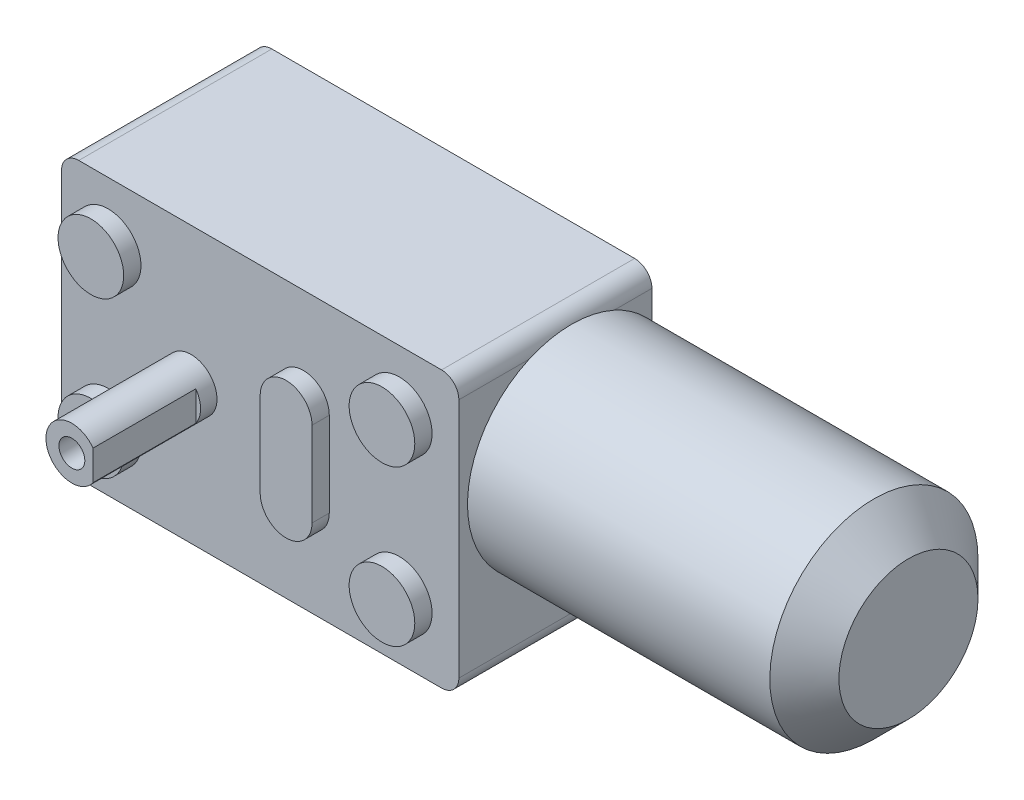
SolidWorks part; units mm, degrees
ref_plane "Front Plane" through (0, 0, 0) normal (1, 0, 0) x (0, 1, 0)
ref_plane "Top Plane" through (0, 0, 0) normal (0, 0, 1) x (0, 1, 0)
ref_plane "Right Plane" through (0, 0, 0) normal (0, 1, 0) x (-1, 0, 0)
sketch "Sketch1" plane through (0, 0, 0) normal (0, 0, 1) x (0, 1, 0)
  line L0 (0, 0) -> (15.3642, 14.4142) construction
  line L1 (-13.95, 15) -> (13.95, 15)
  line L2 (-15.95, 13) -> (-15.95, -29)
  line L3 (-13.95, -31) -> (13.95, -31)
  line L4 (15.95, 13) -> (15.95, -29)
  line L5 (-15.3642, 14.4142) -> (0, 0) construction
  line L6 (-1.7313, -2.45) -> (1.7313, -2.45)
  line L7 (0, -2.45) -> (0, 3) construction
  line L8 (9, 9.6) -> (9, -24.1) construction
  line L9 (9, -24.1) -> (-9, -24.1) construction
  line L10 (-9, -24.1) -> (-9, 9.6) construction
  line L11 (-9, 9.6) -> (9, 9.6) construction
  line L12 (-4.9, -13) -> (4.9, -13) construction
  line L13 (-4.9, -10) -> (4.9, -10)
  line L14 (-4.9, -16) -> (4.9, -16)
  line L15 (7.9, -13) -> (-7.9, -13) construction
  circle A0 centre (0, 0) radius 3
  arc A1 (-15.95, -29) -> (-13.95, -31) centre (-13.95, -29) ccw
  arc A2 (13.95, -31) -> (15.95, -29) centre (13.95, -29) ccw
  arc A3 (13.95, 15) -> (15.95, 13) centre (13.95, 13) cw
  arc A4 (-13.95, 15) -> (-15.95, 13) centre (-13.95, 13) ccw
  circle A5 centre (-9, 9.6) radius 3.8
  circle A6 centre (9, 9.6) radius 3.8
  circle A7 centre (-9, -24.1) radius 3.8
  circle A8 centre (9, -24.1) radius 3.8
  arc A9 (-4.9, -10) -> (-4.9, -16) centre (-4.9, -13) ccw
  arc A10 (4.9, -16) -> (4.9, -10) centre (4.9, -13) ccw
  circle A11 centre (0, 0) radius 1.5
  point P14 (-15.95, -31)
  point P19 (15.95, 15)
  point P22 (-15.95, 15)
  point P32 (0, 15)
  point P33 (0, 9.6)
  point P36 (0, -13)
  dimension "D1" = 6
  dimension "D5" = 2
  dimension "D6" = 7.6
  dimension "D10" = 18
  dimension "D14" = 3
  dimension "D2" = 5.45
  dimension "D3" = 31.9
  dimension "D4" = 46
  dimension "D7" = 12
  dimension "D8" = 5.4
  dimension "D9" = 6.9
  dimension "D11" = 15.8
  dimension "D12" = 6
  dimension "D13" = 15
extrude "Boss-Extrude1" add sketch "Sketch1" along normal blind 13.8 contours L6 A0 | L6 A0 region at (-2.592, -1.3422, 0) region at (2.6718, 0, 0)
extrude "Cut-Extrude1" cut sketch "Sketch1<4>" along normal up to next from offset 1.9 contours L6 A0 region at (2.6718, 0, 0)
sketch "Sketch1<4>" plane through (0, 0, 0) normal (0, 0, 1) x (0, 1, 0) same geometry as "Sketch1"
extrude "Boss-Extrude2" add sketch "Sketch1<5>" along normal blind 2 separate body contours L14 A10 L13 A9 | A8 | A7 | A6 | A5 region at (13, 0, 0) region at (-9.6, -9, 0) region at (-9.6, 9, 0) region at (24.1, -9, 0) region at (24.1, 9, 0)
sketch "Sketch1<5>" plane through (0, 0, 0) normal (0, 0, 1) x (0, 1, 0) same geometry as "Sketch1"
extrude "Boss-Extrude3" add sketch "Sketch1<6>" against normal blind 22.35 separate body contours L1 A4 L2 A1 L3 A2 L4 A3 A10 L14 A9 L13 A8 A7 A6 A5 A0 | A7 | A8 | L14 A10 L13 A9 | L6 A0 A11 | A11 | A5 | A6 | L6 A0 region at (7.9374, 0, 0) region at (-2.592, -1.3422, 0) region at (2.6718, 0, 0) region at (13, 0, 0) region at (-9.6, -9, 0) region at (-9.6, 9, 0) region at (24.1, -9, 0) region at (24.1, 9, 0) region at (0, 0, 0)
sketch "Sketch1<6>" plane through (0, 0, 0) normal (0, 0, 1) x (0, 1, 0) same geometry as "Sketch1"
sketch "Sketch2" plane through (31, 0, 0) normal (1, 0, 0) x (0, 1, 0)
  line L0 (2.95, -1) -> (2.95, 0) construction
  line L1 (-13.95, 0) -> (13.95, 0) construction
  line L2 (13.95, -22.35) -> (13.95, 0) construction
  circle A0 centre (2.95, -13.05) radius 12.05
  point P8 (0, 0)
  dimension "D1" = 24.1
  dimension "D2" = 1
  dimension "D3" = 11
extrude "Boss-Extrude4" add sketch "Sketch2" along normal blind 39
chamfer "Chamfer1" distance 4 angle 45 1 edges at (70, 2.95, -25.1)
